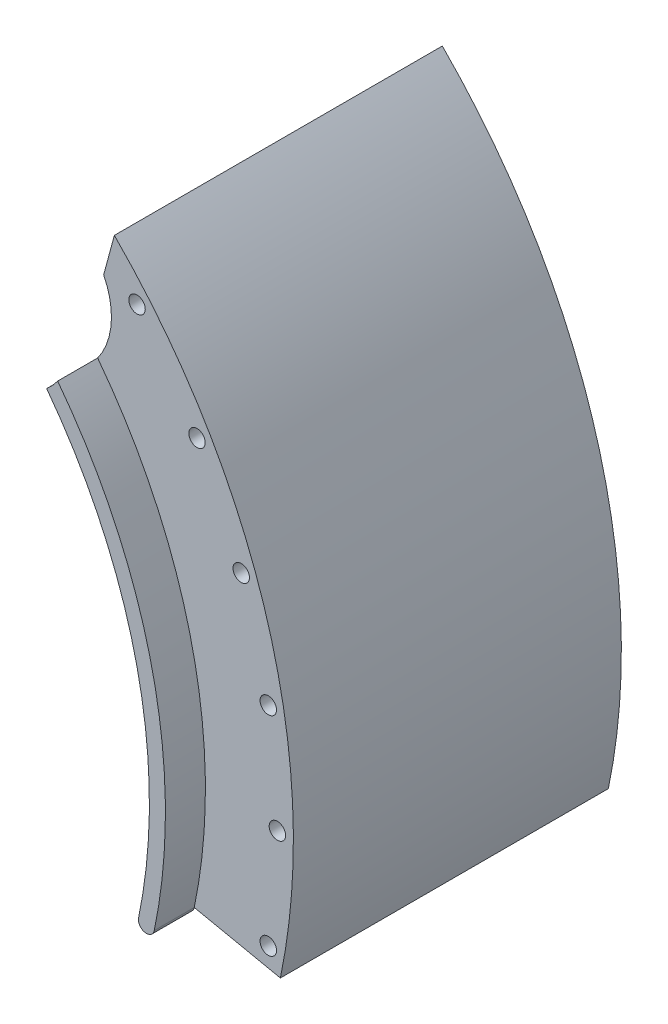
SolidWorks part; units mm, degrees
material "ABS"
ref_plane "Front Plane" through (0, 0, 0) normal (0, 0, 1) x (1, 0, 0)
ref_plane "Top Plane" through (0, 0, 0) normal (0, 1, 0) x (1, 0, 0)
ref_plane "Right Plane" through (0, 0, 0) normal (1, 0, 0) x (0, 0, -1)
sketch "Sketch1" plane through (0, 0, 0) normal (0, 0, 1) x (1, 0, 0)
  line L0 (0, 0) -> (203.2, 0) construction
  line L1 (203.2, 0) -> (209.55, 0) construction
  line L2 (148.1742, 148.1742) -> (143.6841, 143.6841) construction
  line L3 (143.6841, 143.6841) -> (0, 0) construction
  line L4 (203.2, 0) -> (203.2, -50.8) construction
  line L5 (198.9038, -41.5636) -> (205.1195, -42.8625) construction
  line L6 (198.9038, -41.5636) -> (0, 0) construction
  line L7 (203.2, -50.8) -> (205.829, -50.8) construction
  line L8 (160.5177, 124.5966) -> (165.5338, 128.4903) construction
  line L9 (160.5177, 124.5966) -> (0, 0) construction
  arc A0 (203.2, 0) -> (160.5177, 124.5966) centre (0, 0) ccw
  arc A1 (209.55, 0) -> (165.5338, 128.4903) centre (0, 0) ccw
  arc A2 (203.2, 0) -> (198.9038, -41.5636) centre (0, 0) cw
  arc A3 (198.9038, -41.5636) -> (205.1195, -42.8625) centre (202.0116, -42.2131) ccw
  arc A4 (205.1195, -42.8625) -> (209.55, 0) centre (0, 0) ccw
  arc A5 (160.5177, 124.5966) -> (165.5338, 128.4903) centre (163.0257, 126.5435) cw
  arc A6 (160.5177, 124.5966) -> (143.6841, 143.6841) centre (0, 0) ccw construction
  arc A7 (165.5338, 128.4903) -> (148.1742, 148.1742) centre (0, 0) ccw construction
  dimension "D1" = 203.2
  dimension "D2" = 45
  dimension "D3" = 6.35
  dimension "D4" = 50.8
  dimension "D5" = 7.9375
  dimension "D6" = 25.4
extrude "Boss-Extrude2" add sketch "Sketch1" along normal blind 15.875 contours A5 A0 A2 A3 A4 A1 region at (193.9555, 66.4422, 0)
sketch "Sketch3" plane through (0, 0, 15.875) normal (0, 0, 1) x (1, 0, 0)
  line L0 (0, 0) -> (238.125, 0) construction
  line L1 (0, 0) -> (238.125, 0) construction
  line L2 (0, 0) -> (234.5073, 41.35) construction
  line L3 (0, 0) -> (238.125, 0) construction
  line L4 (0, 0) -> (234.5073, -41.35) construction
  line L5 (160.5177, 124.5966) -> (193.1228, 149.9053) construction
  line L6 (160.5177, 124.5966) -> (0, 0) construction
  line L7 (198.9038, -41.5636) -> (239.3061, -50.0062)
  line L8 (198.9038, -41.5636) -> (0, 0) construction
  line L9 (160.5177, 124.5966) -> (173.4144, 172.3237)
  line L10 (0, 0) -> (173.4144, 172.3237) construction
  circle A0 centre (238.125, 0) radius 3.2639
  circle A1 centre (234.5073, 41.35) radius 3.2639
  circle A2 centre (223.7643, 81.4435) radius 3.2639
  circle A3 centre (206.2223, 119.0625) radius 3.2639
  circle A4 centre (182.4143, 153.0638) radius 3.2639
  circle A5 centre (234.5073, -41.35) radius 3.2639
  arc A6 (198.9038, -41.5636) -> (160.5177, 124.5966) centre (0, 0) ccw construction
  arc A7 (198.9038, -41.5636) -> (160.5177, 124.5966) centre (0, 0) ccw
  arc A8 (193.1228, 149.9053) -> (239.3061, -50.0062) centre (0, 0) cw
  arc A9 (193.1228, 149.9053) -> (173.4144, 172.3237) centre (0, 0) ccw
  dimension "D2" = 6.5278
  dimension "D7" = 244.475
  dimension "D8" = 7
  dimension "D1" = 238.125
  dimension "D4" = 10
  dimension "D6" = 10
  dimension "D3" = 5
  dimension "D5" = 2
extrude "Boss-Extrude3" add sketch "Sketch3" along normal blind 130.175
ref_plane "Plane1" through (0, 0, 80.9625) normal (0, 0, -1) x (-1, 0, 0)
mirror "Mirror1" about plane through (0, 0, 80.9625) normal (0, 0, -1) of "Boss-Extrude2"
sketch "Sketch4" plane through (0, 0, 146.05) normal (0, 0, 1) x (1, 0, 0)
  line L0 (0, 0) -> (42.777, 0) construction
  line L1 (0, 0) -> (143.6841, 143.6841) construction
  circle A0 centre (143.6841, 143.6841) radius 28.575
  dimension "D3" = 57.15
  dimension "D1" = 45
  dimension "D2" = 203.2
extrude "Cut-Extrude1" cut sketch "Sketch4" against normal through all both and the other way through all
